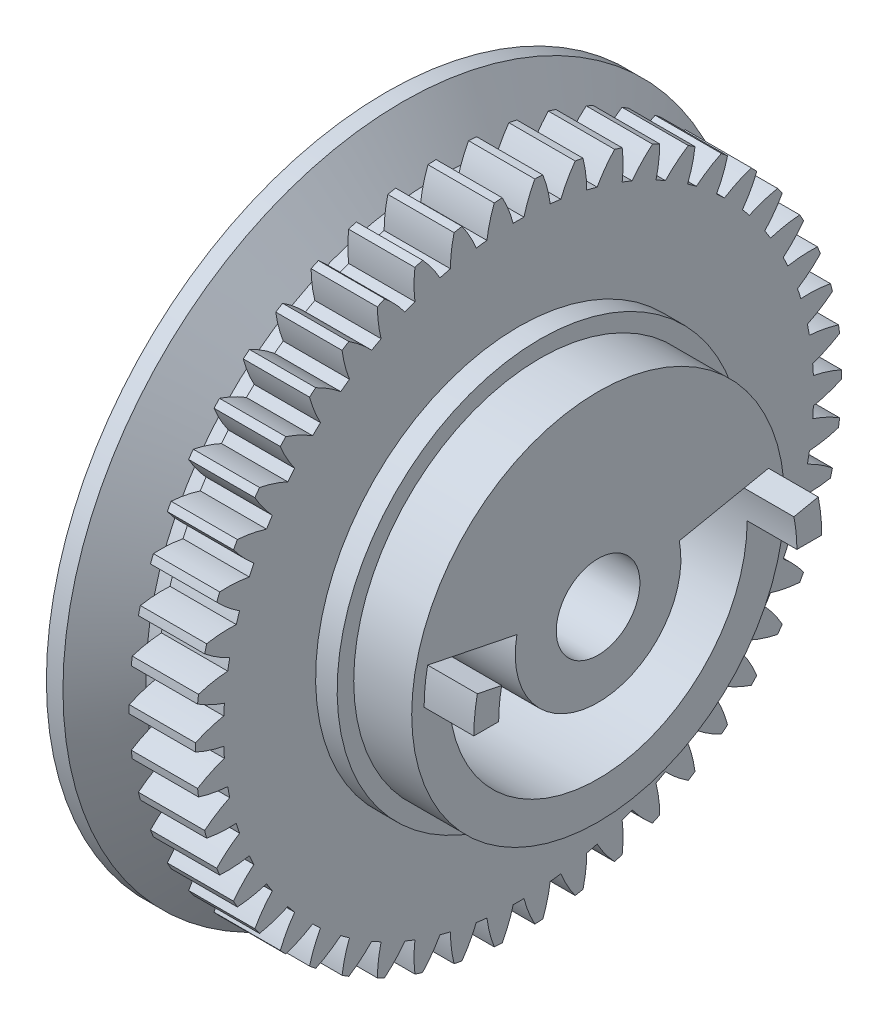
SolidWorks part; units mm, degrees
ref_plane "Plane1" through (0, 0, 0) normal (0, 0, 1) x (1, 0, 0)
ref_plane "Plane2" through (0, 0, 0) normal (0, 1, 0) x (1, 0, 0)
ref_plane "Plane3" through (0, 0, 0) normal (1, 0, 0) x (0, 0, -1)
other "Configuration Table"
sketch "HoldingSke" plane through (0, 0, 0) normal (0, 1, 0) x (1, 0, 0)
  line L0 (0, 0) -> (0.4285, -0.5107)
  line L1 (-15, 0) -> (100, 0) construction
  line L2 (0, 0) -> (-2.1039, 2.3779)
  line L3 (0, 0) -> (-11.863, 4.5341)
  line L4 (0, 0) -> (5.5511, 6.6156)
  line L5 (0, 0) -> (-46.8476, -17.4728)
  line L6 (0, 0) -> (-6.6317, -4.4744)
  line L7 (-2.1039, 2.3779) -> (8.6586, 51.2059)
  line L8 (-76.2, 54.61) -> (-74.4, 54.61)
  line L9 (-71.009, 38.7566) -> (-53.1078, 45.2721)
  line L10 (-76.2, 71.12) -> (104.1128, 71.12)
  line L11 (0, 0) -> (-8, 0)
  line L12 (-76.2, 101.6) -> (-76.147, 101.6)
  line L13 (24.9733, 27.94) -> (52.9518, 28.4284)
  line L14 (24.9733, 27.94) -> (24.9743, 27.94)
  line L15 (24.9733, 27.94) -> (100.4006, 29.5858)
  line L16 (-63.627, -1.5) -> (-12.827, -1.5)
  circle A0 centre (0, 0) radius 5
  circle A1 centre (0, 0) radius 35.624
  circle A2 centre (0, 0) radius 37.5
  circle A3 centre (0, 0) radius 5
  dimension "MHD" = 71.248
  dimension "Hub_dia" = 75
  dimension "Bore" = 10
  dimension "MBD" = 10
  dimension "Num_teeth" = 50
  dimension "Pitch" = 0.6667
  dimension "Overall_len" = 50
  dimension "Show_teeth" = 50
  dimension "Thickness" = 8
  dimension "OAL" = 50.0001
  dimension "T_dim" = 1.8
  dimension "Ap" = 20
  dimension "H" = 19.05
  dimension "Pitch_radius" = 180.3128
  dimension "Width" = 8
  dimension "Backlash" = 0.053
  dimension "Addendum_fac" = 1
  dimension "Dedendum_fac" = 1.25
  dimension "Clearance_fac" = 0.25
  dimension "Dedendum_add" = 0.001
  dimension "Module" = 1.5
sketch "BasProSke" plane through (0, 0, 0) normal (0, 1, 0) x (1, 0, 0)
  line L0 (-10, 0) -> (60, 0) construction
  line L1 (0, 0) -> (0, 39)
  line L2 (0, 0) -> (8, 0)
  line L3 (8, 0) -> (8, 39)
  line L4 (8, 39) -> (0, 39)
  dimension "Thickness" = 8
  dimension "Diameter" = 78
revolve "Base-Revolve" add sketch "BasProSke" angle 360 about L0
sketch "TooCutSke" plane through (0, 0, 0) normal (1, 0, 0) x (0, 0, -1)
  line L1 (0, 0) -> (0, 107) construction
  line L2 (0, 0) -> (-1.2706, 37.4785) construction
  line L3 (0, 0) -> (-4.7073, 74.8207) construction
  line L4 (-1.2706, 37.4785) -> (-2.3537, 37.4103) construction
  arc A0 (0.65, 35.6181) -> (-0.65, 35.6181) centre (0, 0) ccw
  arc A1 (1.9801, 38.9751) -> (-1.9801, 38.9751) centre (0, 0) ccw
  circle A2 centre (0, 0) radius 37.5 construction
  circle A3 centre (0, 0) radius 35.2385 construction
  arc A4 (-0.65, 35.6181) -> (-1.9801, 38.9751) centre (-15.1589, 31.8113) ccw
  arc A5 (1.9801, 38.9751) -> (0.65, 35.6181) centre (15.1589, 31.8113) ccw
  dimension "Root_dia" = 71.248
  dimension "Overcut_dia" = 78.0508
  dimension "Pitch_dia" = 75
  dimension "Base_dia" = 70.4769
  dimension "Flank_rad" = 15
  dimension "Half_ang" = 3.6
  dimension "Half_CT" = 1.0852
extrude "ToothCut" cut sketch "TooCutSke" along normal through all
fillet "Breaks" [suppressed] radius 0.03 tangent propagation no
fillet "RootFillets" [suppressed] radius 0.376
pattern_circular "TeethCuts" count 50 every 7.2 about axis through (-10, 0, 0) along (1, 0, 0) of "ToothCut", "RootFillets", "Breaks"
sketch "HubNeaOneSke" plane through (0, 0, 0) normal (-1, 0, 0) x (0, 0, 1)
  circle A0 centre (0, 0) radius 35.624
  dimension "Diameter" = 71.248
extrude "HubNearOne" [suppressed] add sketch "HubNeaOneSke" along normal blind 42.0001
sketch "HubNeaBotSke" plane through (0, 0, 0) normal (-1, 0, 0) x (0, 0, 1)
  circle A0 centre (0, 0) radius 35.624
  dimension "Diameter" = 71.248
extrude "HubNearBoth" [suppressed] add sketch "HubNeaBotSke" along normal blind 21
ref_plane "FarPln" through (8, 0, 0) normal (1, 0, 0) x (0, 0, -1)
sketch "HubFarSke" plane through (8, 0, 0) normal (1, 0, 0) x (0, 0, -1)
  circle A0 centre (0, 0) radius 35.624
  dimension "Diameter" = 71.248
extrude "HubFar" [suppressed] add sketch "HubFarSke" along normal blind 21
sketch "BorSke" plane through (0, 0, 0) normal (1, 0, 0) x (0, 0, -1)
  circle A0 centre (0, 0) radius 5
  dimension "Diameter" = 10
extrude "Bore" cut sketch "BorSke" along normal mid plane 100.0001
sketch "KeySke" plane through (0, 0, 0) normal (1, 0, 0) x (0, 0, -1)
  line L0 (-2, 0) -> (-2, 6.8)
  line L1 (-2, 6.8) -> (2, 6.8)
  line L2 (2, 6.8) -> (2, 0)
  line L3 (0, 0) -> (0, 34) construction
  line L4 (-2, 0) -> (2, 0)
  dimension "Offset" = 6.8
  dimension "Width" = 4
extrude "Keyway" [suppressed] cut sketch "KeySke" along normal mid plane 100.0001
pattern_circular "Keyway2" [suppressed] count 2 every 90 about axis through (-10, 0, 0) along (1, 0, 0) reverse direction yes
sketch "草图1" plane through (0, 0, 0) normal (0, 0, 1) x (1, 0, 0)
  line L0 (8, 24.5) -> (10.6, 24.5)
  line L1 (8, -5) -> (8, 5) construction
  line L2 (10.6, 24.5) -> (10.6, 22.5)
  line L3 (10.6, 22.5) -> (17.6, 22.5)
  line L4 (17.6, 22.5) -> (17.6, 5)
  line L5 (17.6, 5) -> (8, 5)
  line L6 (8, 5) -> (8, 24.5)
  line L7 (-8, 5) -> (0, 5)
  line L8 (0, 0) -> (-5.2993, 0) construction
  line L9 (0, 0.4829) -> (0, -0.4829) construction
  line L10 (0, 5) -> (0, 35)
  line L11 (0, 35) -> (-2, 35)
  line L12 (-2, 35) -> (-6, 41)
  line L13 (-6, 41) -> (-8, 41)
  line L14 (-8, 41) -> (-8, 5)
  line L15 (0, 0) -> (0, 107) construction
  dimension "D1" = 45
  dimension "D2" = 2
  dimension "D3" = 2.6
  dimension "D4" = 7
  dimension "D5" = 10
  dimension "D6" = 82
  dimension "D7" = 70
  dimension "D8" = 2
  dimension "D9" = 2
  dimension "D10" = 8
revolve "旋转1" add sketch "草图1" angle 360 about L8
ref_axis "基准轴1" through (17.6, 0, 0) along (-1, 0, 0)
sketch "草图2" plane through (-8, 0, 0) normal (-1, 0, 0) x (0, 0, 1)
  circle A0 centre (0, 0) radius 7.5
  dimension "D1" = 15
extrude "切除-拉伸1" cut sketch "草图2" against normal blind 5.5
sketch "草图10" plane through (-8, 0, 0) normal (-1, 0, 0) x (0, 0, 1)
  circle A0 centre (0, 0) radius 5.05
  dimension "D1" = 10.1
extrude "切除-拉伸5" cut sketch "草图10" against normal through all
sketch "草图3" plane through (-8, 0, 0) normal (-1, 0, 0) x (0, 0, 1)
  line L0 (0, 0) -> (0, -18.4341) construction
  arc A0 (-7.5, -6.6144) -> (7.5, -6.6144) centre (0, 0) ccw
  arc A1 (-13.5, -11.9059) -> (13.5, -11.9059) centre (0, 0) ccw
  arc A2 (-13.5, -11.9059) -> (-7.5, -6.6144) centre (-10.5, -9.2601) cw
  arc A3 (7.5, -6.6144) -> (13.5, -11.9059) centre (10.5, -9.2601) cw
  dimension "D1" = 10
  dimension "D2" = 18
  dimension "D3" = 15
extrude "切除-拉伸2" cut sketch "草图3" against normal through all
sketch "草图4" plane through (17.6, 0, 0) normal (1, 0, 0) x (0, 0, -1)
  line L0 (14, 0) -> (-14, 0) construction
  circle A0 centre (-14, 0) radius 1.1
  circle A1 centre (14, 0) radius 1.1
  point P8 (0, 0)
  dimension "D3" = 2.2
  dimension "D1" = 28
extrude "切除-拉伸3" cut sketch "草图4" against normal up to surface (25.6 mm away) up to face at (-8, -10.1301, 0)
sketch "草图5" plane through (17.6, 0, 0) normal (1, 0, 0) x (0, 0, -1)
  line L0 (-17.6363, 3.6) -> (-9.798, 2)
  line L1 (17.6363, 3.6) -> (9.798, 2)
  line L2 (-7.6844, 0) -> (0, 0) construction
  arc A1 (9.798, 2) -> (-9.798, 2) centre (0, 0) cw
  arc A3 (17.6363, 3.6) -> (-17.6363, 3.6) centre (0, 0) cw
  arc A6 (-13.5, -11.9059) -> (13.5, -11.9059) centre (0, 0) ccw construction
  arc A7 (-7.5, -6.6144) -> (7.5, -6.6144) centre (0, 0) ccw construction
  dimension "D1" = 2
extrude "切除-拉伸4" cut sketch "草图5" against normal offset from surface (13.6 mm away) 12 up to face at (-8, -1.1, -14)
sketch "草图7" plane through (17.6, 0, 0) normal (1, 0, 0) x (0, 0, -1)
  line L0 (17.6363, 3.6) -> (20.5757, 4.2)
  line L1 (18, 0) -> (21, 0)
  line L2 (-17.6363, 3.6) -> (-20.5757, 4.2)
  line L3 (-18, 0) -> (-21, 0)
  circle A0 centre (0, 0) radius 18
  circle A1 centre (0, 0) radius 21
  arc A2 (-17.6363, 3.6) -> (17.6363, 3.6) centre (0, 0) ccw construction
  arc M10 (17.6363, 3.6) -> (-17.6363, 3.6) centre (0, 0) cw
  dimension "D1" = 3
extrude "凸台-拉伸1" add sketch "草图7" along normal blind 6 contours L2 A1 L3 M10 | L1 A1 L0 M10 region at (17.6, 1.9605, -19.4067) region at (17.6, 1.9605, 19.4067)
equation "' \"Module@HoldingSke\" = 6.35"
equation "' \"Num_teeth@HoldingSke\" = 12"
equation "' \"Ap@HoldingSke\" =  20"
equation "' \"Ap@HoldingSke\" = 20"
equation "' \"Width@HoldingSke\" = 0.5 * 25.4"
equation "' \"Hub_dia@HoldingSke\"= 1 * 25.4"
equation "' \"Hub_dia@HoldingSke\" = 1 * 25.4"
equation "' \"Overall_len@HoldingSke\" = 1.0 * 25.4"
equation "' \"Bore@HoldingSke\" = 0.75 * 25.4"
equation "' \"T_dim@HoldingSke\" = 0.1 * 25.4"
equation "' \"Width@KeySke\" = 0.25 * 25.4"
equation "' \"Show_teeth@HoldingSke\" = 13"
equation "' \"Backlash@HoldingSke\" = 0.009 * 25.4"
equation "' \"Addendum_fac@HoldingSke\" = 1.0"
equation "' \"Dedendum_fac@HoldingSke\" = 1.25"
equation "' \"Dedendum_add@HoldingSke\" = 0.00005 * 25.4"
equation "' \"Clearance_fac@HoldingSke\" = 0.25"
equation "\"Pitch@HoldingSke\" = 1 / \"Module@HoldingSke\""
equation "\"Overcut_dia@TooCutSke\" = (\"Num_teeth@HoldingSke\" + 2 * \"Addendum_fac@HoldingSke\") / \"Pitch@HoldingSke\" + 0.002 * 25.4"
equation "\"Pitch_dia@TooCutSke\" = \"Num_teeth@HoldingSke\" / \"Pitch@HoldingSke\""
equation "\"Base_dia@TooCutSke\" = \"Num_teeth@HoldingSke\" / \"Pitch@HoldingSke\" * cos((\"Ap@HoldingSke\"  * 3.14159265 / 180))"
equation "\"Root_dia@TooCutSke\" = (\"Num_teeth@HoldingSke\" + 2) / \"Pitch@HoldingSke\" - 2 * (\"Addendum_fac@HoldingSke\" + \"Dedendum_fac@HoldingSke\") / \"Pitch@HoldingSke\" - \"Dedendum_add@HoldingSke\" * 2"
equation "\"Half_ang@TooCutSke\" = 180 / \"Num_teeth@HoldingSke\""
equation "\"Half_CT@TooCutSke\" = \"Num_teeth@HoldingSke\" / \"Pitch@HoldingSke\" * sin((3.14159265 / 2 / \"Num_teeth@HoldingSke\")) / 2 - 7 * \"Backlash@HoldingSke\" / 4"
equation "\"Flank_rad@TooCutSke\" = \"Num_teeth@HoldingSke\" / \"Pitch@HoldingSke\" / 5"
equation "\"Radius@RootFillets\" = \"Clearance_fac@HoldingSke\" / \"Pitch@HoldingSke\" + \"Dedendum_add@HoldingSke\""
equation "\"Break_rad@Breaks\" = 0.02 / \"Pitch@HoldingSke\""
equation "\"Thickness@HoldingSke\" = \"Width@HoldingSke\""
equation "\"OAL@HoldingSke\" = \"Thickness@HoldingSke\""
equation "\"MHD@HoldingSke\" = (\"Num_teeth@HoldingSke\" + 2) / \"Pitch@HoldingSke\" - 2 * (\"Addendum_fac@HoldingSke\" + \"Dedendum_fac@HoldingSke\")  / \"Pitch@HoldingSke\" - \"Dedendum_add@HoldingSke\" * 2"
equation "\"MBD@HoldingSke\" = (\"Num_teeth@HoldingSke\" + 2) / \"Pitch@HoldingSke\" - 2 * (\"Addendum_fac@HoldingSke\" + \"Dedendum_fac@HoldingSke\")  / \"Pitch@HoldingSke\" - \"Dedendum_add@HoldingSke\" * 2 - 0.002 * 25.4"
equation "\"MHD@HoldingSke\" = ((sgn( \"MHD@HoldingSke\" - \"Hub_dia@HoldingSke\" )-1)*( \"MHD@HoldingSke\" - \"Hub_dia@HoldingSke\" ))/-2+ \"Hub_dia@HoldingSke\""
equation "\"MBD@HoldingSke\" = ((sgn( \"MBD@HoldingSke\" - \"Bore@HoldingSke\" )-1)*( \"MBD@HoldingSke\" - \"Bore@HoldingSke\" ))/-2+ \"Bore@HoldingSke\""
equation "\"OAL@HoldingSke\" = ((sgn( \"OAL@HoldingSke\" - \"Overall_len@HoldingSke\" )+1)*( \"OAL@HoldingSke\" - \"Overall_len@HoldingSke\" ))/2 + \"Overall_len@HoldingSke\" + 0.000002 * 25.4"
equation "\"Num_teeth@TeethCuts\" = int( \"Show_teeth@HoldingSke\" ) + 1"
equation "\"Num_teeth@TeethCuts\" = ((sgn( \"Num_teeth@TeethCuts\" - \"Num_teeth@HoldingSke\" )-1)*( \"Num_teeth@TeethCuts\" - \"Num_teeth@HoldingSke\" ))/-2+ \"Num_teeth@HoldingSke\""
equation "\"Num_teeth@TeethCuts\" = ((sgn( \"Num_teeth@TeethCuts\" - 2.0)+1)*( \"Num_teeth@TeethCuts\" - 2.0))/2 +2.0"
equation "\"Angle@TeethCuts\" = 360.0 / \"Num_teeth@HoldingSke\""
equation "\"Diameter@BasProSke\" = (\"Num_teeth@HoldingSke\" + 2 * \"Addendum_fac@HoldingSke\") / \"Pitch@HoldingSke\""
equation "\"Thickness@BasProSke\"  = \"Thickness@HoldingSke\""
equation "' \"Fillet_rad@BasProSke\" =  \"Thickness@HoldingSke\" * 0.05"
equation "' \"Fillet_rad@BasProSke\" = \"Thickness@HoldingSke\" * 0.05"
equation "\"MHD@HoldingSke\" = ((sgn( \"MHD@HoldingSke\" - \"Root_dia@TooCutSke\" )-1)*( \"MHD@HoldingSke\" - \"Root_dia@TooCutSke\" ))/-2+ \"Root_dia@TooCutSke\""
equation "\"Diameter@HubNeaOneSke\" = \"MHD@HoldingSke\""
equation "\"Length@HubNearOne\" = \"OAL@HoldingSke\" - \"Thickness@BasProSke\""
equation "\"Diameter@HubNeaBotSke\" = \"MHD@HoldingSke\""
equation "\"Length@HubNearBoth\" = ( \"OAL@HoldingSke\" - \"Thickness@BasProSke\" ) / 2.0"
equation "\"Thickness@FarPln\" = \"Thickness@BasProSke\""
equation "\"Diameter@HubFarSke\" = \"MHD@HoldingSke\""
equation "\"Length@HubFar\" = ( \"OAL@HoldingSke\" - \"Thickness@BasProSke\" ) / 2.0"
equation "\"Diameter@BorSke\" = \"MBD@HoldingSke\""
equation "\"D1@Bore\" = \"OAL@HoldingSke\" * 2.0"
equation "\"D1@Keyway\" = \"OAL@HoldingSke\" * 2.0"
equation "\"Offset@KeySke\" = \"T_dim@HoldingSke\" + \"MBD@HoldingSke\" / 2.0"
